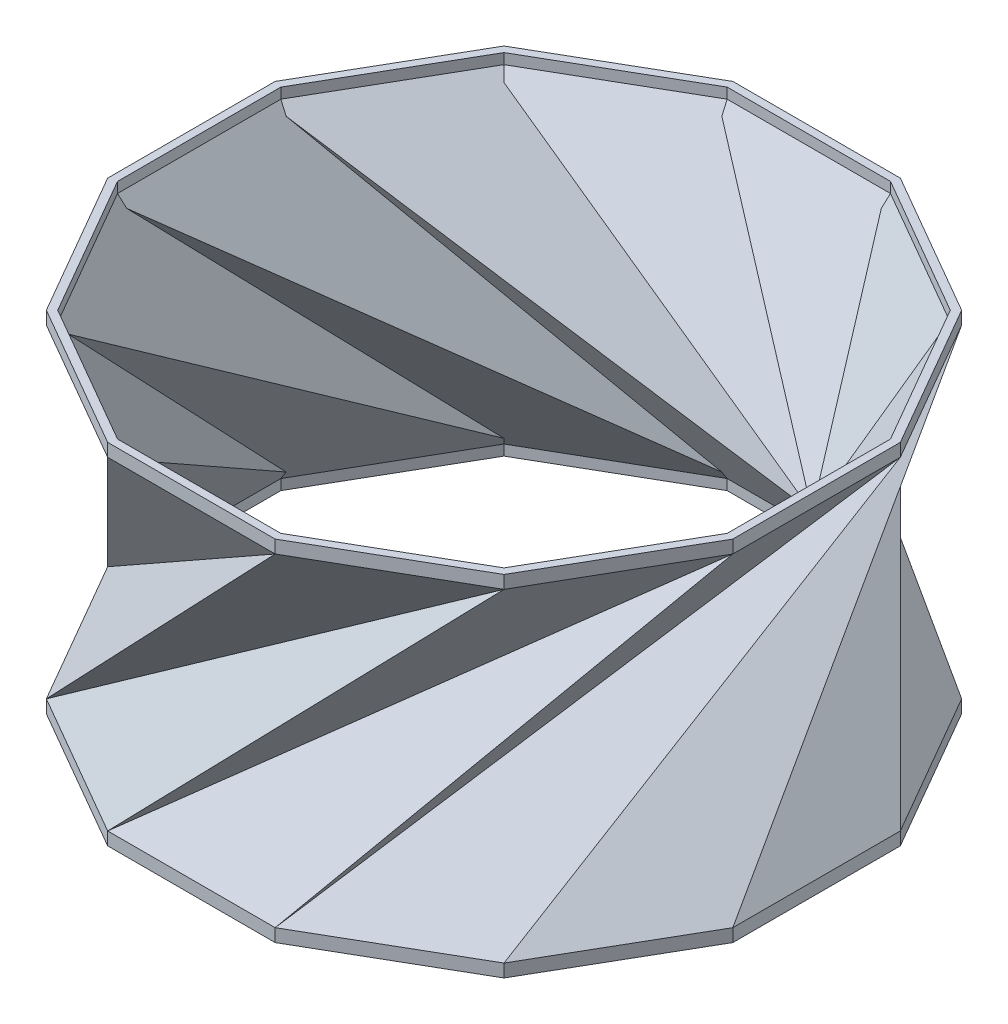
SolidWorks part; units mm, degrees
ref_plane "정면" through (0, 0, 0) normal (0, 0, 1) x (1, 0, 0)
ref_plane "윗면" through (0, 0, 0) normal (0, 1, 0) x (1, 0, 0)
ref_plane "우측면" through (0, 0, 0) normal (1, 0, 0) x (0, 0, -1)
sketch "스케치1" plane through (0, 0, 0) normal (0, 1, 0) x (1, 0, 0)
  line L0 (0, -55) -> (0, 55) construction
  line L1 (17.6777, -17.6777) -> (24.1481, -6.4705)
  line L2 (24.1481, -6.4705) -> (24.1481, 6.4705)
  line L3 (24.1481, 6.4705) -> (17.6777, 17.6777)
  line L4 (17.6777, 17.6777) -> (6.4705, 24.1481)
  line L5 (6.4705, 24.1481) -> (-6.4705, 24.1481)
  line L6 (-6.4705, 24.1481) -> (-17.6777, 17.6777)
  line L7 (-17.6777, 17.6777) -> (-24.1481, 6.4705)
  line L8 (-24.1481, 6.4705) -> (-24.1481, -6.4705)
  line L9 (-24.1481, -6.4705) -> (-17.6777, -17.6777)
  line L10 (-17.6777, -17.6777) -> (-6.4705, -24.1481)
  line L11 (-6.4705, -24.1481) -> (6.4705, -24.1481)
  line L12 (6.4705, -24.1481) -> (17.6777, -17.6777)
  circle A0 centre (0, 0) radius 25 construction
  dimension "D1" = 50
extrude "보스-돌출1" add sketch "스케치1" along normal blind 25
ref_plane "평면1" through (-8.0494, 11.3835, 13.9419) normal (-0.4082, 0.5774, 0.7071) x (0.9129, 0.2582, 0.3162)
sketch "스케치2" plane through (-8.0494, 11.3835, 13.9419) normal (-0.4082, 0.5774, 0.7071) x (0.9129, 0.2582, 0.3162)
  line L0 (-10.5473, -11.1803) -> (28.1826, 8.1846)
  line L1 (28.1826, 8.1846) -> (1.7296, -15.2726)
ref_plane "평면2" through (2.1568, -3.0502, 3.7357) normal (-0.4082, 0.5774, -0.7071) x (-0.9129, -0.2582, 0.3162)
sketch "스케치3" plane through (2.1568, -3.0502, 3.7357) normal (-0.4082, 0.5774, -0.7071) x (-0.9129, -0.2582, 0.3162)
  line L0 (21.7276, 11.1803) -> (-4.7254, 34.6375)
ref_plane "평면3" through (-17.6777, 0, 17.6777) normal (0.8165, 0.5774, 0) x (0, 0, -1)
sketch "스케치4" plane through (-17.6777, 0, 17.6777) normal (0.8165, 0.5774, 0) x (0, 0, -1)
  line L0 (0, 0) -> (-6.4705, -6.4705) construction
  line L1 (0, 0) -> (-6.4705, 6.4705) construction
  line L2 (0, 0) -> (-6.4705, -6.4705)
  line L3 (0, 0) -> (-6.4705, 6.4705)
  line L4 (-6.4705, 6.4705) -> (-6.4705, -6.4705)
  point P2 (-6.6316, -6.4705)
  point P4 (0, 0)
extrude "컷-돌출1" cut sketch "스케치4" along normal up to vertex (43.3013 mm away) up to point (17.6777, 25, 17.6777)
pattern_circular "원형 패턴1" count 12 over 360 about axis through (0, 25, 0) along (0, 1, 0) of "컷-돌출1"
sketch "스케치5" plane through (0, 25, 0) normal (0, 1, 0) x (1, 0, 0)
  line L12 (6.4705, -24.1481) -> (17.6777, -17.6777)
  line L13 (17.6777, -17.6777) -> (24.1481, -6.4705)
  line L14 (24.1481, -6.4705) -> (24.1481, 6.4705)
  line L15 (24.1481, 6.4705) -> (17.6777, 17.6777)
  line L16 (17.6777, 17.6777) -> (6.4705, 24.1481)
  line L17 (6.4705, 24.1481) -> (-6.4705, 24.1481)
  line L18 (-6.4705, 24.1481) -> (-17.6777, 17.6777)
  line L19 (-17.6777, 17.6777) -> (-24.1481, 6.4705)
  line L20 (-24.1481, 6.4705) -> (-24.1481, -6.4705)
  line L21 (-24.1481, -6.4705) -> (-17.6777, -17.6777)
  line L22 (-17.6777, -17.6777) -> (-6.4705, -24.1481)
  line L23 (-6.4705, -24.1481) -> (6.4705, -24.1481)
  line L24 (6.4705, -24.1481) -> (17.6777, -17.6777)
  line L25 (17.6777, -17.6777) -> (24.1481, -6.4705)
  line L26 (24.1481, -6.4705) -> (24.1481, 6.4705)
  line L27 (24.1481, 6.4705) -> (17.6777, 17.6777)
  line L28 (17.6777, 17.6777) -> (6.4705, 24.1481)
  line L29 (6.4705, 24.1481) -> (-6.4705, 24.1481)
  line L30 (-6.4705, 24.1481) -> (-17.6777, 17.6777)
  line L31 (-17.6777, 17.6777) -> (-24.1481, 6.4705)
  line L32 (-24.1481, 6.4705) -> (-24.1481, -6.4705)
  line L33 (-24.1481, -6.4705) -> (-17.6777, -17.6777)
  line L34 (-17.6777, -17.6777) -> (-6.4705, -24.1481)
  line L35 (-6.4705, -24.1481) -> (6.4705, -24.1481)
  dimension "D1" = 0
extrude "보스-돌출2" add sketch "스케치5" along normal blind 1
sketch "스케치6" plane through (0, 0, 0) normal (0, -1, 0) x (1, 0, 0)
  line L12 (17.6777, 17.6777) -> (6.4705, 24.1481)
  line L13 (6.4705, 24.1481) -> (-6.4705, 24.1481)
  line L14 (-6.4705, 24.1481) -> (-17.6777, 17.6777)
  line L15 (-17.6777, 17.6777) -> (-24.1481, 6.4705)
  line L16 (-24.1481, 6.4705) -> (-24.1481, -6.4705)
  line L17 (-24.1481, -6.4705) -> (-17.6777, -17.6777)
  line L18 (-17.6777, -17.6777) -> (-6.4705, -24.1481)
  line L19 (-6.4705, -24.1481) -> (6.4705, -24.1481)
  line L20 (6.4705, -24.1481) -> (17.6777, -17.6777)
  line L21 (17.6777, -17.6777) -> (24.1481, -6.4705)
  line L22 (24.1481, -6.4705) -> (24.1481, 6.4705)
  line L23 (24.1481, 6.4705) -> (17.6777, 17.6777)
  line L24 (17.6777, 17.6777) -> (6.4705, 24.1481)
  line L25 (6.4705, 24.1481) -> (-6.4705, 24.1481)
  line L26 (-6.4705, 24.1481) -> (-17.6777, 17.6777)
  line L27 (-17.6777, 17.6777) -> (-24.1481, 6.4705)
  line L28 (-24.1481, 6.4705) -> (-24.1481, -6.4705)
  line L29 (-24.1481, -6.4705) -> (-17.6777, -17.6777)
  line L30 (-17.6777, -17.6777) -> (-6.4705, -24.1481)
  line L31 (-6.4705, -24.1481) -> (6.4705, -24.1481)
  line L32 (6.4705, -24.1481) -> (17.6777, -17.6777)
  line L33 (17.6777, -17.6777) -> (24.1481, -6.4705)
  line L34 (24.1481, -6.4705) -> (24.1481, 6.4705)
  line L35 (24.1481, 6.4705) -> (17.6777, 17.6777)
  dimension "D1" = 0
extrude "보스-돌출3" add sketch "스케치6" along normal blind 1
shell "쉘1" thickness 0.6 removed face at (0, 26, 0) removed face at (0, -1, 0)
